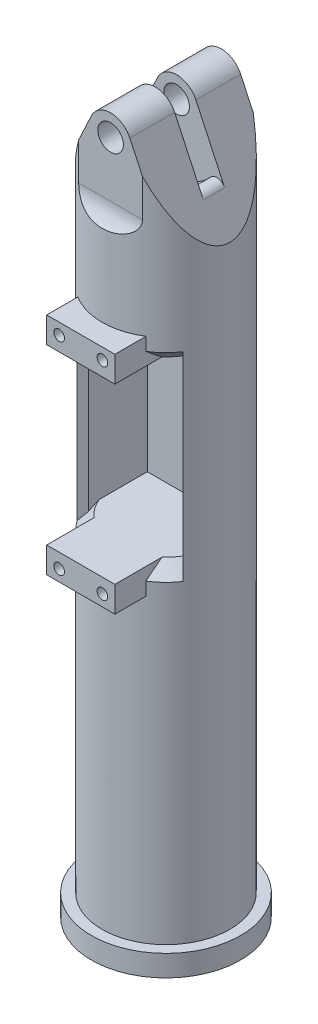
SolidWorks part; units mm, degrees
ref_plane "Front Plane" through (0, 0, 0) normal (0, 0, 1) x (1, 0, 0)
ref_plane "Top Plane" through (0, 0, 0) normal (0, 1, 0) x (1, 0, 0)
ref_plane "Right Plane" through (0, 0, 0) normal (1, 0, 0) x (0, 0, -1)
sketch "Sketch1" plane through (0, 0, 0) normal (0, 1, 0) x (1, 0, 0)
  circle A0 centre (0, 0) radius 15
  dimension "D1" = 30
extrude "Boss-Extrude1" add sketch "Sketch1" along normal blind 170
sketch "Sketch2" plane through (0, 0, 0) normal (0, 0, 1) x (1, 0, 0)
  line L0 (-10.5, 160) -> (-10.5, 182.2206)
  line L1 (-10.5, 182.2206) -> (10.5, 182.2206)
  line L2 (10.5, 182.2206) -> (10.5, 160)
  line L3 (15, 170) -> (-15, 170) construction
  arc A0 (-10.5, 160) -> (10.5, 160) centre (0, 160) ccw
  dimension "D1" = 21
  dimension "D2" = 10
extrude "Cut-Extrude1" cut sketch "Sketch2" against normal mid plane 5
sketch "Sketch3" plane through (0, 0, 0) normal (1, 0, 0) x (0, 0, -1)
  line L0 (-15, 170) -> (-13, 170)
  line L1 (15, 170) -> (-15, 170) construction
  line L2 (-13, 170) -> (-13, 152)
  line L3 (-15, 170) -> (-15, 147.5279)
  line L4 (-15, 170) -> (-15, 0) construction
  line L5 (0, 170) -> (0, 145.7961) construction
  line L6 (15, 170) -> (15, 147.5279)
  line L7 (13, 170) -> (13, 152)
  line L8 (15, 170) -> (13, 170)
  arc A0 (-15, 147.5279) -> (-13, 152) centre (-19, 152) ccw
  arc A1 (15, 147.5279) -> (13, 152) centre (19, 152) cw
  dimension "D1" = 12
  dimension "D2" = 18
  dimension "D3" = 2
extrude "Cut-Extrude2" cut sketch "Sketch3" against normal through all both and the other way through all
sketch "Sketch4" plane through (0, 0, 13) normal (0, 0, 1) x (1, 0, 0)
  line L0 (7.4833, 170) -> (-7.4833, 170) construction
  circle A0 centre (0, 165) radius 3
  dimension "D1" = 6
  dimension "D2" = 5
extrude "Cut-Extrude3" cut sketch "Sketch4" against normal through all
sketch "Sketch5" plane through (0, 0, 13) normal (0, 0, 1) x (1, 0, 0)
  line L0 (-4.5315, 167.1131) -> (-15, 144.6634)
  line L1 (-15, 144.6634) -> (-15, 175.2765)
  line L2 (-15, 175.2765) -> (15, 175.2765)
  line L3 (15, 175.2765) -> (15, 144.6634)
  line L4 (15, 144.6634) -> (4.5315, 167.1131)
  line L5 (0, 165) -> (0, 175.2765) construction
  line L6 (7.4833, 170) -> (-7.4833, 170) construction
  arc A0 (4.5315, 167.1131) -> (-4.5315, 167.1131) centre (0, 165) ccw
  dimension "D1" = 50
  dimension "D2" = 30
extrude "Cut-Extrude4" cut sketch "Sketch5" against normal through all
fillet "Fillet1" radius 2 2 edges at (-9.7108, 156.0062, 0) (9.7108, 156.0062, 0)
sketch "Sketch6" plane through (0, 0, 0) normal (0, 0, 1) x (1, 0, 0)
  line L0 (0, 0) -> (0, 102) construction
  line L1 (-8, 75.585) -> (8, 75.585)
  line L2 (-8, 75.585) -> (-8, 128.415)
  line L3 (-8, 128.415) -> (8, 128.415)
  line L4 (8, 75.585) -> (8, 128.415)
  line L5 (-8, 75.585) -> (8, 128.415) construction
  line L6 (-8, 128.415) -> (8, 75.585) construction
  point P0 (0, 102)
  dimension "D1" = 52.83
  dimension "D2" = 16
  dimension "D3" = 102
extrude "Boss-Extrude2" add sketch "Sketch6" along normal blind 20
sketch "Sketch7" plane through (0, 0, 20) normal (0, 0, 1) x (1, 0, 0)
  line L0 (0, 128.415) -> (0, 75.585) construction
  line L1 (8, 128.415) -> (-8, 128.415) construction
  line L2 (-8, 75.585) -> (8, 75.585) construction
  line L4 (-11.0853, 122.35) -> (11.0853, 122.35)
  line L5 (-11.0853, 122.35) -> (-11.0853, 81.65)
  line L6 (-11.0853, 81.65) -> (11.0853, 81.65)
  line L7 (11.0853, 122.35) -> (11.0853, 81.65)
  line L8 (-11.0853, 122.35) -> (11.0853, 81.65) construction
  line L9 (-11.0853, 81.65) -> (11.0853, 122.35) construction
  point P6 (0, 102)
  dimension "D1" = 40.7
extrude "Cut-Extrude5" cut sketch "Sketch7" against normal blind 26.7
sketch "Sketch8" plane through (0, 0, 20) normal (0, 0, 1) x (1, 0, 0)
  line L0 (-5.08, 125.749) -> (-5.08, 78.251) construction
  line L3 (-5.08, 125.749) -> (-8, 125.749) construction
  line L4 (-8, 128.415) -> (-8, 122.35) construction
  line L5 (5.08, 125.749) -> (8, 125.749) construction
  line L6 (8, 122.35) -> (8, 128.415) construction
  line L7 (-5.08, 125.749) -> (-5.08, 128.415) construction
  line L8 (8, 128.415) -> (-8, 128.415) construction
  line L9 (-5.08, 78.251) -> (-5.08, 75.585) construction
  line L10 (-8, 75.585) -> (8, 75.585) construction
  circle A0 centre (-5.08, 125.749) radius 1.25
  circle A1 centre (-5.08, 78.251) radius 1.25
  circle A2 centre (5.08, 125.749) radius 1.25
  circle A3 centre (5.08, 78.251) radius 1.25
  dimension "D1" = 47.498
  dimension "D2" = 2.5
  dimension "D4" = 10.16
extrude "Cut-Extrude6" cut sketch "Sketch8" against normal blind 6
sketch "Sketch9" plane through (0, 0, 0) normal (0, -1, 0) x (1, 0, 0)
  circle A0 centre (0, 0) radius 17.5
  dimension "D1" = 35
extrude "Boss-Extrude3" add sketch "Sketch9" against normal blind 5
sketch "Sketch10" plane through (0, 5, 0) normal (0, 1, 0) x (1, 0, 0)
  line L0 (0, 0) -> (0, 13) construction
  circle A0 centre (0, 13) radius 1.5
  circle A1 centre (13, 0) radius 1.5
  circle A2 centre (0, -13) radius 1.5
  circle A3 centre (-13, 0) radius 1.5
  point P13 (0, 0)
  dimension "D1" = 3
  dimension "D2" = 13
  dimension "D3" = 4
extrude "Cut-Extrude7" cut sketch "Sketch10" against normal through all
chamfer "Chamfer1" distance 3 angle 45 6 edges at (-9.6297, 122.35, 11.5009) (9.6297, 122.35, 11.5009) (11.0853, 102, 10.1053) (9.6297, 81.65, 11.5009) (-9.6297, 81.65, 11.5009) (-11.0853, 102, 10.1053) first distance on face at (0, 122.35, 9.0494) first distance on face at (11.0853, 102, 1.7026) first distance on face at (0, 81.65, 9.0494) first distance on face at (-11.0853, 102, 1.7026)
